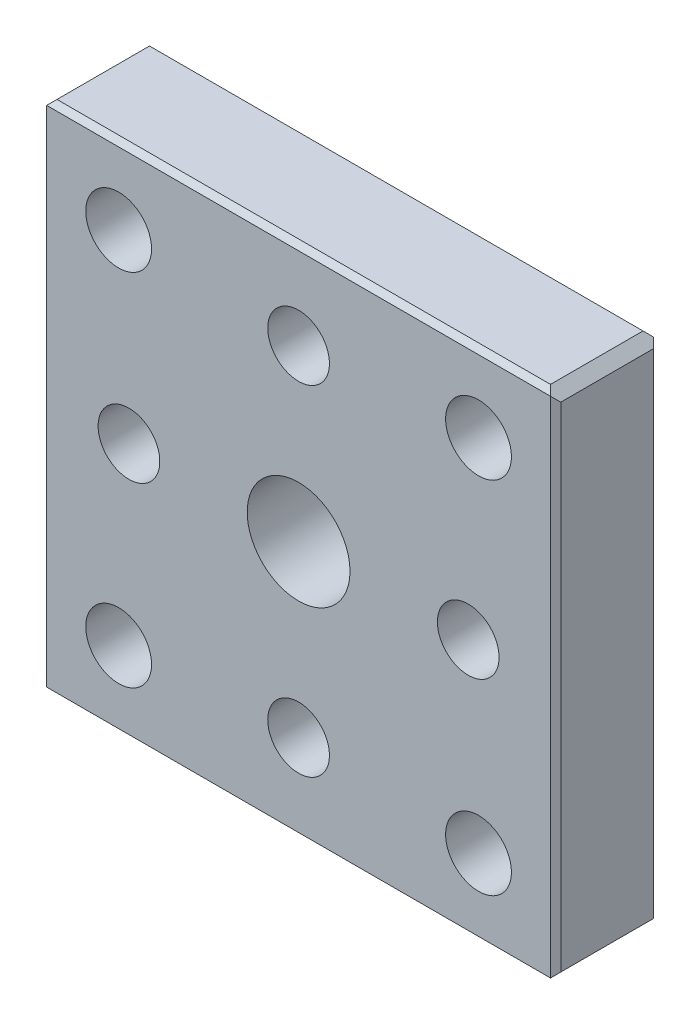
SolidWorks part; units mm, degrees
material "Plain Carbon Steel"
ref_plane "Front Plane" through (0, 0, 0) normal (0, 0, 1) x (1, 0, 0)
ref_plane "Top Plane" through (0, 0, 0) normal (0, 1, 0) x (1, 0, 0)
ref_plane "Right Plane" through (0, 0, 0) normal (1, 0, 0) x (0, 0, -1)
sketch "Sketch1" plane through (0, 0, 0) normal (0, 0, 1) x (1, 0, 0)
  line L1 (-25, -25) -> (25, -25)
  line L2 (-25, -25) -> (-25, 25)
  line L3 (-25, 25) -> (25, 25)
  line L4 (25, -25) -> (25, 25)
  line L5 (-25, -25) -> (25, 25) construction
  line L6 (-25, 25) -> (25, -25) construction
  point P0 (0, 0)
  dimension "D1" = 50
  dimension "D2" = 50
extrude "Boss-Extrude1" add sketch "Sketch1" along normal mid plane 10
hole_wizard "M6 Clearance Hole1" positions "Sketch4" profile "Sketch3" hole size "M6" standard "ISO" end condition through all
sketch "Sketch4" plane through (0, 0, 5) normal (0, 0, 1) x (1, 0, 0)
  line L0 (-25, 0) -> (25, 0) construction
  line L1 (-25, 25) -> (-25, -25) construction
  line L2 (25, -25) -> (25, 25) construction
  line L4 (0, 25) -> (0, -25) construction
  line L5 (25, 25) -> (-25, 25) construction
  line L6 (-25, -25) -> (25, -25) construction
  point P0 (-17.5, 17.5)
  point P2 (17.5, 17.5)
  point P4 (17.5, -17.5)
  point P6 (-17.5, -17.5)
  dimension "D1" = 35
  dimension "D2" = 35
sketch "Sketch3" plane through (-17.5, 17.5, 5) normal (1, 0, 0) x (0, -1, 0)
  line L0 (0, 0) -> (0, 10)
  line L1 (0, 10) -> (3.2, 10)
  line L2 (3.2, 10) -> (3.2, 0)
  line L5 (3.2, 0) -> (0, 0)
  line L11 (0, -6.35) -> (0, 107.95) construction
  dimension "Thru Hole Dia." = 6.4
  dimension "Thru Hole Depth" = 10
sketch "Sketch5" plane through (0, 0, 5) normal (0, 0, 1) x (1, 0, 0)
  circle A0 centre (0, 0) radius 5
  dimension "D1" = 10
extrude "Cut-Extrude1" cut sketch "Sketch5" against normal up to next
sketch "Sketch6" plane through (0, 0, -5) normal (0, 0, -1) x (-1, 0, 0)
  circle A0 centre (0, 0) radius 19
  dimension "D1" = 38
chamfer "Chamfer1" distance 1 angle 45 4 edges at (25, -25, 0) (-25, -25, 0) (-25, 25, 0) (25, 25, 0)
chamfer "Chamfer2" distance 0.5 angle 45 8 edges at (0, -25, 5) (0, -25, -5) (0, 25, -5) (0, 25, 5) (25, 0, -5) (25, 0, 5) (-25, 0, -5) (-25, 0, 5)
hole_wizard "Ø6.0 (6) Diameter Hole1" positions "Sketch9" profile "Sketch8" hole size "Ø6.0" standard "ISO" end condition through all
sketch "Sketch9" plane through (0, 0, -5) normal (0, 0, -1) x (-1, 0, 0)
  point P0 (-16.5, 0)
  point P3 (0, 16.5)
  point P6 (16.5, 0)
  point P9 (0, -16.5)
sketch "Sketch8" plane through (16.5, 0, -5) normal (1, 0, 0) x (0, 1, 0)
  line L0 (0, 0) -> (0, 10)
  line L1 (0, 10) -> (3, 10)
  line L2 (3, 10) -> (3, 0)
  line L5 (3, 0) -> (0, 0)
  line L11 (0, -6.35) -> (0, 107.95) construction
  dimension "Thru Hole Dia." = 6
  dimension "Thru Hole Depth" = 10
sketch "Sketch12" plane through (0, 0, -5) normal (0, 0, -1) x (-1, 0, 0)
  circle A1 centre (16.5, 0) radius 6.25 construction
  circle A3 centre (0, -16.5) radius 6.25 construction
  circle A5 centre (-16.5, 0) radius 6.25 construction
  circle A7 centre (0, 16.5) radius 6.25 construction
  circle A9 centre (16.5, 0) radius 6.25
  circle A11 centre (0, -16.5) radius 6.25
  circle A13 centre (-16.5, 0) radius 6.25
  circle A15 centre (0, 16.5) radius 6.25
extrude "Cut-Extrude2" cut sketch "Sketch12" against normal blind 2
